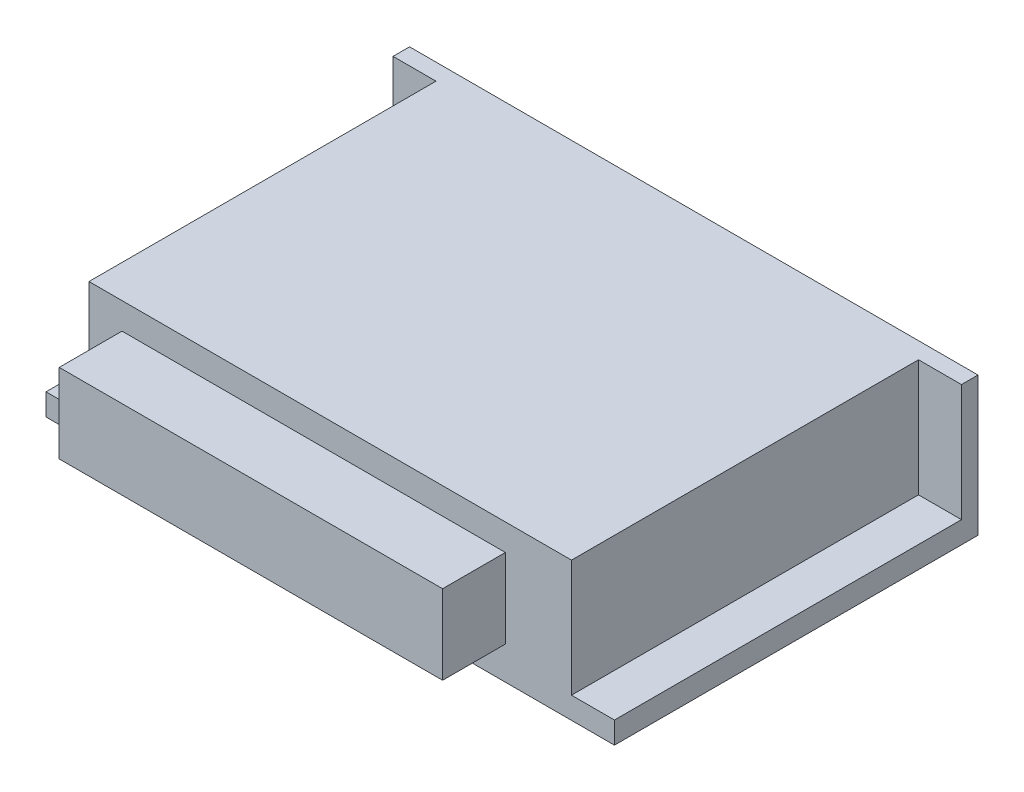
SolidWorks part; units mm, degrees
ref_plane "Front" through (0, 0, 0) normal (0, 0, 1) x (1, 0, 0)
ref_plane "Top" through (0, 0, 0) normal (0, 1, 0) x (1, 0, 0)
ref_plane "Right" through (0, 0, 0) normal (1, 0, 0) x (0, 0, -1)
sketch "Sketch1" plane through (0, 0, 0) normal (0, 1, 0) x (1, 0, 0)
  line L1 (-43, -27.5) -> (43, -27.5)
  line L2 (-43, -27.5) -> (-43, 27.5)
  line L3 (-43, 27.5) -> (43, 27.5)
  line L4 (43, -27.5) -> (43, 27.5)
  line L5 (-43, -27.5) -> (43, 27.5) construction
  line L6 (-43, 27.5) -> (43, -27.5) construction
  point P0 (0, 0)
  dimension "D1" = 86
  dimension "D2" = 55
extrude "Boss-Extrude1" add sketch "Sketch1" along normal blind 3.3
sketch "Sketch2" plane through (0, 3.3, 0) normal (0, 1, 0) x (1, 0, 0)
  line L0 (43, 27.5) -> (-43, 27.5) construction
  line L1 (-48.75, 27.5) -> (48.75, 27.5)
  line L2 (-36.5, 25) -> (-36.5, -27.5)
  line L3 (-36.5, -27.5) -> (36.5, -27.5)
  line L4 (36.5, 25) -> (36.5, -27.5)
  line L5 (-43, 27.5) -> (-43, -27.5) construction
  line L6 (-43, -27.5) -> (43, -27.5) construction
  line L7 (43, -27.5) -> (43, 27.5) construction
  line L8 (-43, 27.5) -> (43, 27.5)
  line L9 (-43, 27.5) -> (-43, 25)
  line L10 (-43, 25) -> (-36.5, 25)
  line L11 (43, 27.5) -> (43, 25)
  line L12 (36.5, 25) -> (43, 25)
  point P6 (0, -27.5)
  line M10 (43, -27.5) -> (43, 27.5)
  line M11 (43, 27.5) -> (-43, 27.5)
  line M12 (-43, 27.5) -> (-43, -27.5)
  line M13 (-43, -27.5) -> (43, -27.5)
  dimension "D1" = 6.5
  dimension "D2" = 2.5
extrude "Boss-Extrude2" add sketch "Sketch2" along normal offset from surface (17.7 mm away) 21 contours L4 L12 L10 L2 M10 M11 M12 M13 region at (0, 3.3, -0.2108) up to face at (0, 0, 0)
sketch "Sketch3" plane through (0, 0, 27.5) normal (0, 0, 1) x (1, 0, 0)
  line L1 (-31.5, 5) -> (26.5, 5)
  line L2 (-31.5, 5) -> (-31.5, 17)
  line L3 (-31.5, 17) -> (26.5, 17)
  line L4 (26.5, 5) -> (26.5, 17)
  line L5 (-36.5, 21) -> (-36.5, 3.3) construction
  line L6 (36.5, 21) -> (-36.5, 21) construction
  dimension "D1" = 58
  dimension "D2" = 5
  dimension "D3" = 4
  dimension "D4" = 12
extrude "Boss-Extrude3" add sketch "Sketch3" along normal blind 9.5
